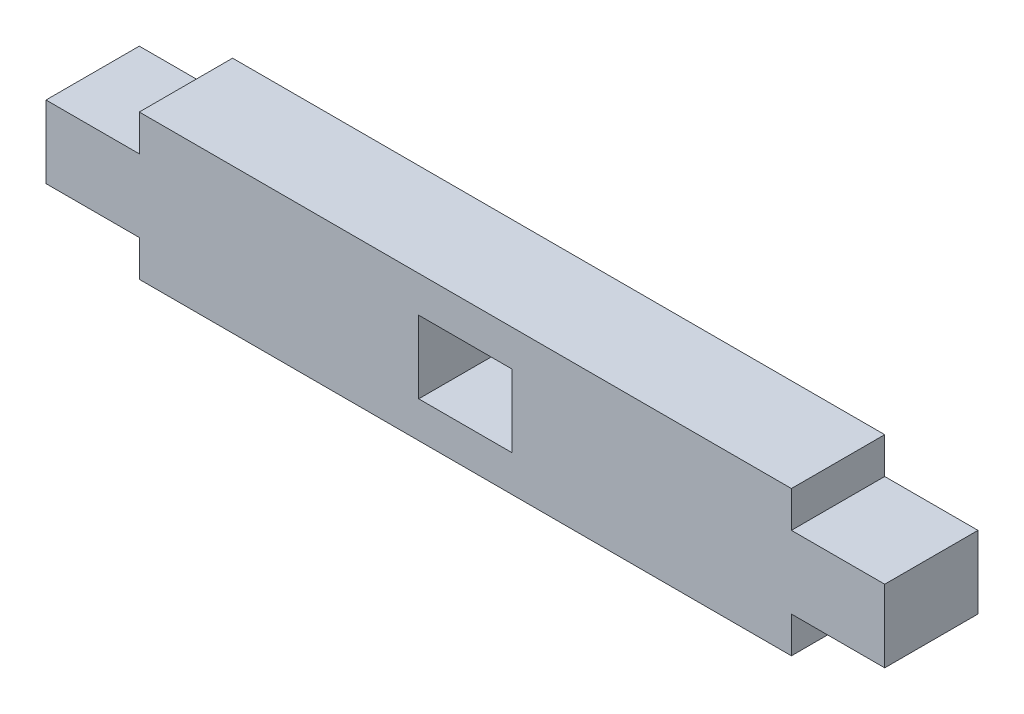
SolidWorks part; units mm, degrees
ref_plane "Front Plane" through (0, 0, 0) normal (0, 0, 1) x (1, 0, 0)
ref_plane "Top Plane" through (0, 0, 0) normal (0, 1, 0) x (1, 0, 0)
ref_plane "Right Plane" through (0, 0, 0) normal (1, 0, 0) x (0, 0, -1)
sketch "Sketch1" plane through (0, 0, 0) normal (0, 0, 1) x (1, 0, 0)
  line L0 (-18, 8) -> (18, 8)
  line L1 (0, -55) -> (0, 55) construction
  line L2 (18, 8) -> (18, 6)
  line L3 (18, 6) -> (23.15, 6)
  line L4 (23.15, 6) -> (23.15, 2)
  line L5 (23.15, 2) -> (18, 2)
  line L6 (18, 2) -> (18, 0)
  line L7 (55, 0) -> (-55, 0) construction
  line L8 (18, 0) -> (-18, 0)
  line L9 (0, 22.3415) -> (0, -9.0349) construction
  line L10 (-18, 2) -> (-18, 0)
  line L11 (-23.15, 2) -> (-18, 2)
  line L12 (-23.15, 6) -> (-23.15, 2)
  line L13 (-18, 6) -> (-23.15, 6)
  line L14 (-18, 8) -> (-18, 6)
  point P16 (0, 0)
  point P21 (0, 8)
  dimension "D1" = 8
  dimension "D2" = 4
  dimension "D3" = 36
  dimension "D4" = 5.15
extrude "Boss-Extrude1" add sketch "Sketch1" along normal blind 5.15
sketch "Sketch3" plane through (0, 0, 5.15) normal (0, 0, 1) x (1, 0, 0)
  line L0 (0, 8.3794) -> (0, -6.0522) construction
  line L2 (-23.15, 4) -> (23.15, 4) construction
  line L3 (-23.15, 6) -> (-23.15, 2) construction
  line L4 (23.15, 2) -> (23.15, 6) construction
  line L6 (-2.575, 6) -> (2.575, 6)
  line L7 (-2.575, 6) -> (-2.575, 2)
  line L8 (-2.575, 2) -> (2.575, 2)
  line L9 (2.575, 6) -> (2.575, 2)
  point P13 (2.575, 4)
  point P14 (0, 6)
  dimension "D1" = 5.15
  dimension "D2" = 4
extrude "Cut-Extrude1" cut sketch "Sketch3" against normal through all
